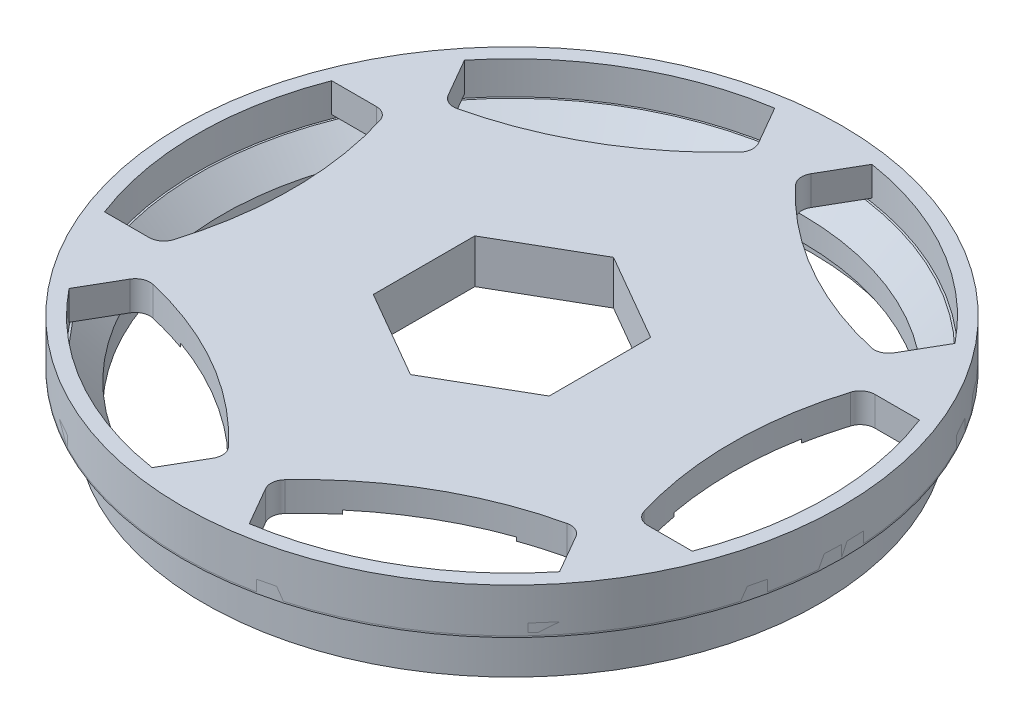
SolidWorks part; units mm, degrees
ref_plane "Ebene vorne" through (0, 0, 0) normal (0, 0, 1) x (1, 0, 0)
ref_plane "Ebene oben" through (0, 0, 0) normal (0, 1, 0) x (1, 0, 0)
ref_plane "Ebene rechts" through (0, 0, 0) normal (1, 0, 0) x (0, 0, -1)
sketch "Skizze1" plane through (0, 0, 0) normal (0, 1, 0) x (1, 0, 0)
  circle A0 centre (0, 0) radius 44
  dimension "D1" = 88
extrude "Aufsatz-Linear austragen1" add sketch "Skizze1" along normal blind 4
sketch "Skizze2" plane through (0, 4, 0) normal (0, 1, 0) x (1, 0, 0)
  line L0 (-32.5715, 15.5) -> (-71.0776, 15.5)
  line L1 (-32.5715, -15.5) -> (-71.0776, -15.5)
  line L2 (-71.0776, 15.5) -> (-71.0776, -15.5)
  circle A0 centre (-78, 0) radius 48
  circle M2 centre (0, 0) radius 44
  dimension "D1" = 78
  dimension "D2" = 96
  dimension "D3" = 31
  dimension "D4" = 15.5
extrude "Schnitt-Linear austragen2" cut sketch "Skizze2" against normal blind 10 contours L1 A0 L0 M2 region at (-36.9648, 4, 0)
sketch "Skizze4" plane through (0, 4, 0) normal (0, 1, 0) x (1, 0, 0)
  circle A0 centre (0, 0) radius 21.0071
extrude "Aufsatz-Linear austragen4" add sketch "Skizze4" against normal blind 6
pattern_circular "Kreismuster1" count 6 over 360 about axis through (0, 0, 0) along (0, 1, 0) of "Schnitt-Linear austragen2"
sketch "Skizze3" plane through (0, 0, 0) normal (0, -1, 0) x (1, 0, 0)
  line L1 (12, 6.9282) -> (0, 13.8564)
  line L2 (0, 13.8564) -> (-12, 6.9282)
  line L3 (-12, 6.9282) -> (-12, -6.9282)
  line L4 (-12, -6.9282) -> (0, -13.8564)
  line L5 (0, -13.8564) -> (12, -6.9282)
  line L6 (12, -6.9282) -> (12, 6.9282)
  circle A0 centre (0, 0) radius 12 construction
extrude "Schnitt-Linear austragen3" cut sketch "Skizze3" against normal blind 10 and the other way blind 4
fillet "Verrundung1" radius 2 12 edges at (-32.5715, 2, 15.5) (-2.8623, 2, 35.9577) (2.8623, 2, 35.9577) (29.7091, 2, 20.4577) (32.5715, 2, 15.5) (32.5715, 2, -15.5) (29.7091, 2, -20.4577) (2.8623, 2, -35.9577) (-2.8623, 2, -35.9577) (-29.7091, 2, -20.4577) (-32.5715, 2, -15.5) (-29.7091, 2, 20.4577)
sketch "Skizze5" plane through (13.4234, 0, 7.75) normal (-0.866, 0, -0.5) x (-0.5, 0, 0.866)
  line L0 (-34.0256, 0) -> (-41.1795, 0) construction
  circle A0 centre (-39, 0) radius 1.6
sketch "Skizze6" plane through (0, 0, -15.5) normal (0, 0, 1) x (1, 0, 0)
  line L0 (34.0256, 0) -> (41.1795, 0) construction
  circle A0 centre (39, 0) radius 1.6
sketch "Skizze8" plane through (0, 4, 0) normal (0, 1, 0) x (1, 0, 0)
  circle A0 centre (0, 0) radius 45
  circle A1 centre (0, 0) radius 43
extrude "Aufsatz-Linear austragen2" add sketch "Skizze8" against normal blind 6
sketch "Skizze9" plane through (0, -2, 0) normal (0, -1, 0) x (1, 0, 0)
  circle A0 centre (0, 0) radius 45
  circle A1 centre (0, 0) radius 39.5
extrude "Aufsatz-Linear austragen3" add sketch "Skizze9" along normal blind 7 and the other way blind 1.5 separate body
chamfer "Fase1" distance 3.25 angle 45 1 edges at (0, -0.5, -39.5)
sketch "Skizze7" plane through (0, 0, 0) normal (0, -1, 0) x (1, 0, 0)
  circle A0 centre (0, 0) radius 32
  circle A1 centre (0, 0) radius 21.5
extrude "Schnitt-Linear austragen7" cut sketch "Skizze7" against normal blind 0.5
sketch "Skizze10" plane through (0, -9, 0) normal (0, -1, 0) x (1, 0, 0)
  circle A0 centre (0, 0) radius 42
  circle A1 centre (0, 0) radius 50
extrude "Schnitt-Linear austragen9" cut sketch "Skizze10" against normal blind 6 contours A1 | A0
sketch "Skizze11" plane through (0, -9, 0) normal (0, -1, 0) x (1, 0, 0)
  circle A0 centre (0, 0) radius 40.9
  circle A1 centre (-1.9486, 1.7726) radius 30
extrude "Schnitt-Linear austragen10" cut sketch "Skizze11" against normal blind 2
chamfer "Fase2" distance 3 angle 15 1 edges at (0, -3, -45) first distance on face at (0, -3, -45)
chamfer "Fase3" distance 2 angle 45 1 edges at (0, -2, 21.0071)
fillet "Verrundung2" radius 1 1 edges at (0, -3, -42)
